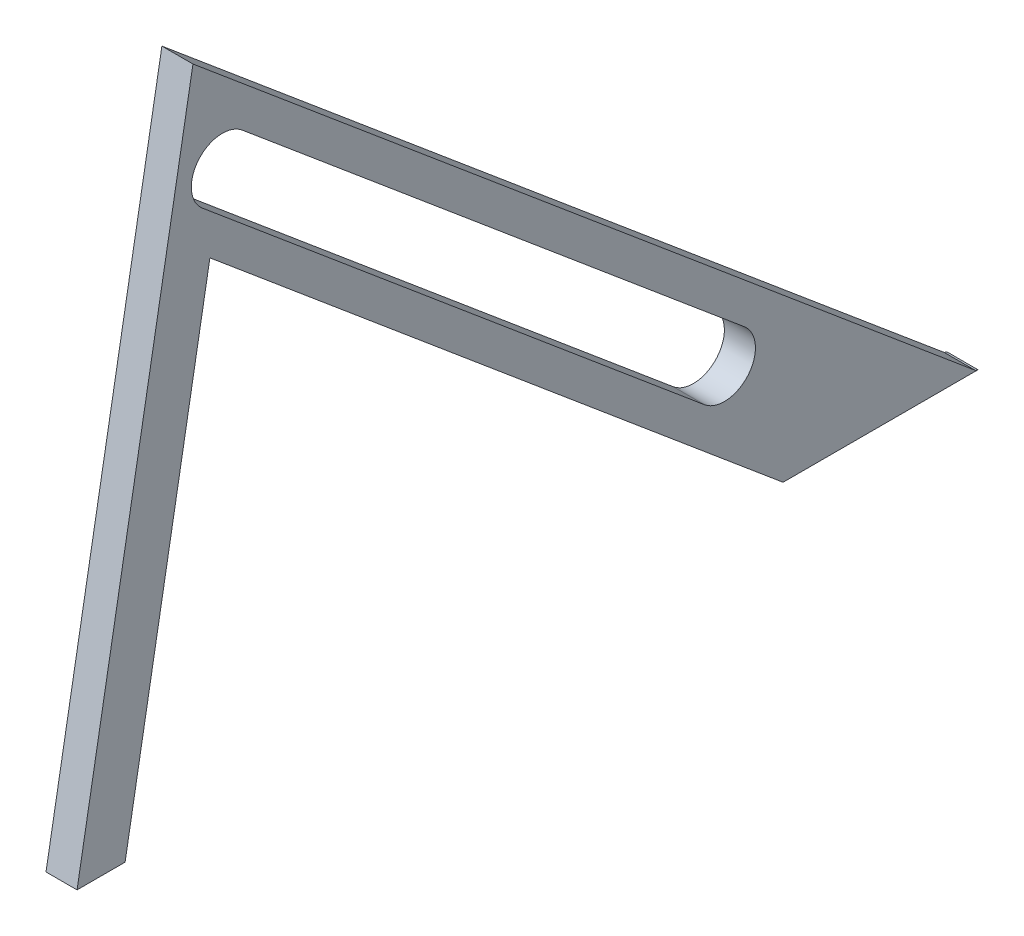
SolidWorks part; units mm, degrees
ref_plane "Front Plane" through (0, 0, 0) normal (0, 0, 1) x (1, 0, 0)
ref_plane "Top Plane" through (0, 0, 0) normal (0, 1, 0) x (1, 0, 0)
ref_plane "Right Plane" through (0, 0, 0) normal (1, 0, 0) x (0, 0, -1)
sketch "Sketch1" plane through (0, 0, 0) normal (1, 0, 0) x (0, 0, -1)
  line L0 (-444.5, 0) -> (444.5, 0) construction
  line L1 (-444.5, 0) -> (-397.0929, 268.859) construction
  line L2 (-397.0929, 268.859) -> (-444.5, 0)
  line L3 (-397.0929, 268.859) -> (-77.079, 0.3354)
  line L4 (-397.0929, 268.859) -> (-397.0929, 0) construction
  line L9 (-77.079, 0.3354) -> (-75.9791, 0)
  line L10 (-237.0859, 134.5972) -> (-286.7402, 75.4216) construction
  line L16 (-286.7402, 75.4216) -> (-413.7726, 182.0144) construction
  line L17 (-286.7402, 75.4216) -> (-96.4268, -84.2704) construction
  line L18 (-397.0929, 0) -> (-397.0929, -231.14) construction
  line L19 (-245.2493, 124.8685) -> (-320.9886, 188.4213) construction
  line L20 (-261.5762, 105.4109) -> (-354.6717, 183.5274) construction
  line L21 (-269.7396, 95.6822) -> (-390.1563, 196.7238)
  line L22 (-269.7396, 95.6822) -> (-155.71, 0)
  line L23 (-420.7965, 134.4295) -> (-382.6698, 127.7067) construction
  line L24 (-401.7331, 131.0681) -> (-424.844, 0) construction
  line L25 (-401.7331, 131.0681) -> (-390.1563, 196.7238) construction
  line L26 (-390.1563, 196.7238) -> (-424.844, 0)
  line L28 (-328.6917, 194.8849) -> (-345.0185, 175.4274) construction
  line L29 (-336.8551, 185.1562) -> (-385.0633, 225.6076) construction
  line L30 (-336.8551, 185.1562) -> (-179.7174, 53.3019) construction
  line L31 (-385.0633, 225.6076) -> (-179.7174, 53.3019) construction
  line L32 (-376.8999, 235.3364) -> (-171.554, 63.0307)
  line L33 (-393.2267, 215.8788) -> (-187.8808, 43.5732)
  line L34 (-444.5, 0) -> (-424.844, 0)
  line L35 (-155.71, 0) -> (-75.9791, 0)
  line L36 (-387.6098, 211.1657) -> (-379.9703, 254.4914) construction
  arc A2 (-376.8999, 235.3364) -> (-393.2267, 215.8788) centre (-385.0633, 225.6076) ccw
  arc A3 (-187.8808, 43.5732) -> (-171.554, 63.0307) centre (-179.7174, 53.3019) ccw
  point P4 (0, 0)
  point P32 (-282.3903, 139.4548)
  dimension "D1" = 889
  dimension "D7" = 12.7
  dimension "D2" = 231.14
  dimension "D3" = 499.999
  dimension "D4" = 25.4
  dimension "D5" = 12.7
  dimension "D6" = 12.7
  dimension "D8" = 19.656
  dimension "D10" = 40
  dimension "D11" = 80
extrude "Boss-Extrude1" add sketch "Sketch1" along normal blind 12.7
